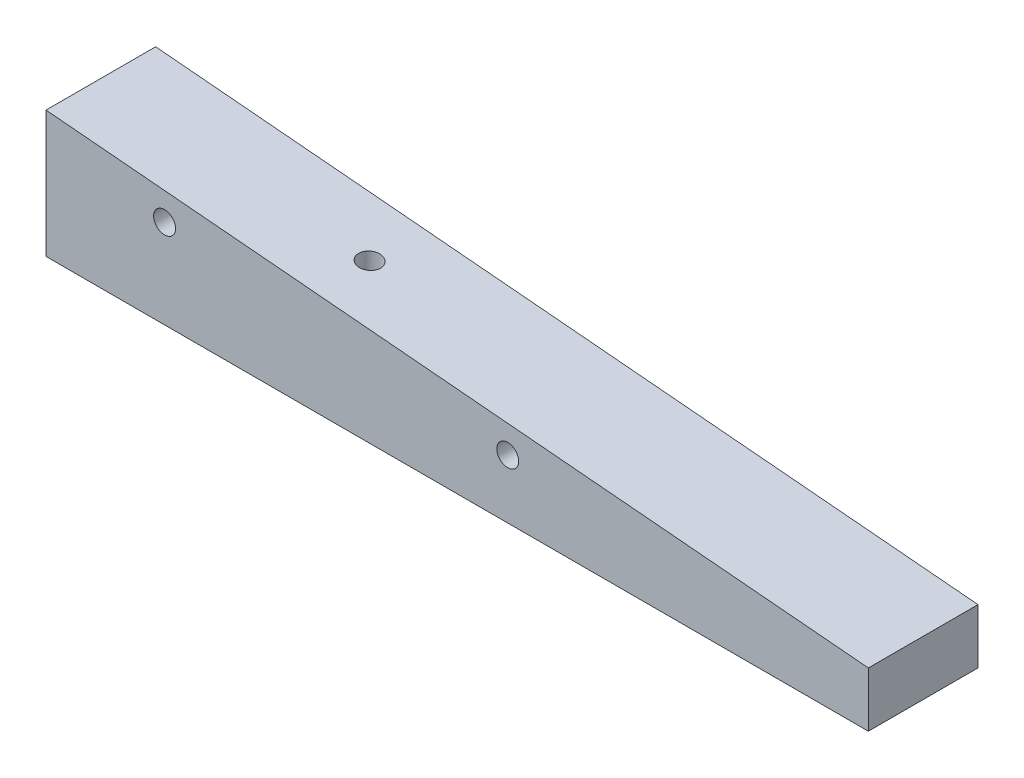
SolidWorks part; units mm, degrees
ref_plane "Front Plane" through (0, 0, 0) normal (0, 0, 1) x (1, 0, 0)
ref_plane "Top Plane" through (0, 0, 0) normal (0, 1, 0) x (1, 0, 0)
ref_plane "Right Plane" through (0, 0, 0) normal (1, 0, 0) x (0, 0, -1)
sketch "Sketch1" plane through (0, 0, 0) normal (0, 0, 1) x (1, 0, 0)
  line L2 (100.9722, 0) -> (-49.0278, 13.1233)
  line L5 (-49.0278, -10) -> (100.9722, -10)
  line L6 (100.9722, -10) -> (100.9722, 0)
  line L7 (-49.0278, 13.1233) -> (-49.0278, -10)
  dimension "D2" = 5
  dimension "D3" = 10
extrude "Boss-Extrude1" add sketch "Sketch1" along normal mid plane 20
sketch "Sketch2" plane through (0, -10, 0) normal (0, -1, 0) x (1, 0, 0)
  circle A0 centre (0, 0) radius 2
  dimension "D1" = 4
extrude "Cut-Extrude1" cut sketch "Sketch2" against normal through all
sketch "Sketch3" plane through (0, 0, 10) normal (0, 0, 1) x (1, 0, 0)
  line L0 (-26.9639, 11.193) -> (-27.3996, 6.212) construction
  line L2 (35.6299, 5.7167) -> (35.1941, 0.7357) construction
  line L3 (100.9722, 0) -> (-49.0278, 13.1233) construction
  circle A0 centre (-27.3996, 6.212) radius 2
  circle A1 centre (35.1941, 0.7357) radius 2
  point P8 (35.6732, 6.212)
  dimension "D5" = 4
  dimension "D6" = 4
  dimension "D1" = 90
  dimension "D2" = 90
  dimension "D3" = 5
  dimension "D4" = 5
extrude "Cut-Extrude2" cut sketch "Sketch3" against normal through all both and the other way through all
